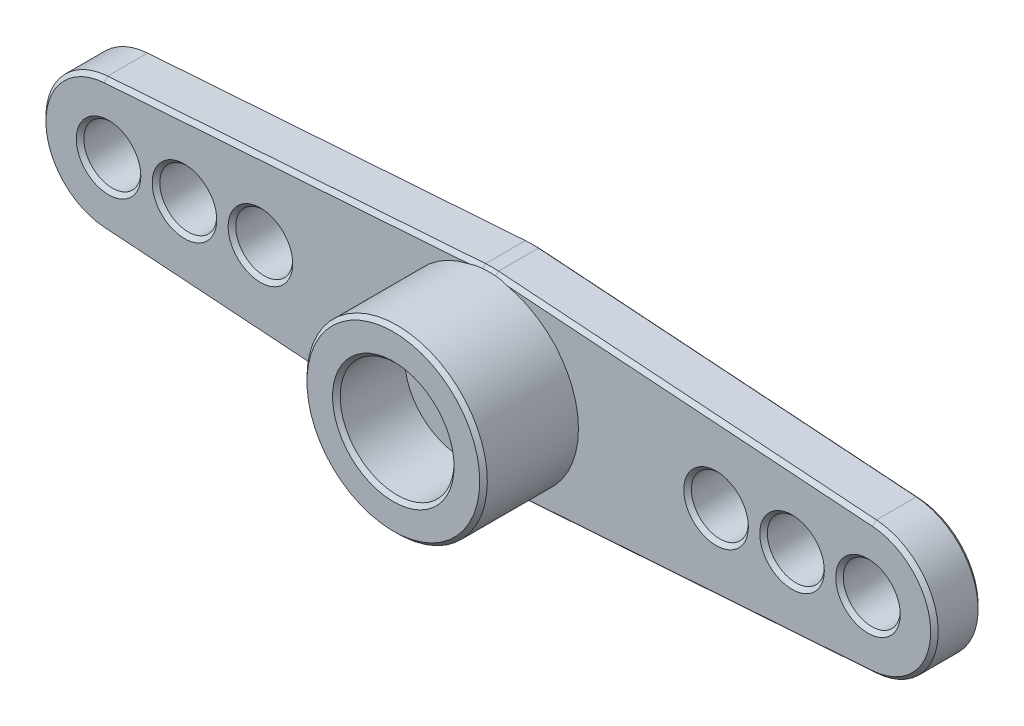
SolidWorks part; units mm, degrees
ref_plane "前视基准面" through (0, 0, 0) normal (0, 0, 1) x (1, 0, 0)
ref_plane "上视基准面" through (0, 0, 0) normal (0, 1, 0) x (1, 0, 0)
ref_plane "右视基准面" through (0, 0, 0) normal (1, 0, 0) x (0, 0, -1)
sketch "草图1" plane through (0, 0, 0) normal (0, 0, 1) x (1, 0, 0)
  line L0 (0.343, 4.888) -> (20.245, 3.4914)
  line L1 (0, 4.9) -> (0, -7.2758) construction
  line L2 (0, 0) -> (11.5337, 0) construction
  line L3 (0.343, -4.888) -> (20.245, -3.4914)
  line L4 (-0.343, -4.888) -> (-20.245, -3.4914)
  line L5 (-0.343, 4.888) -> (-20.245, 3.4914)
  arc A0 (-0.343, -4.888) -> (0.343, -4.888) centre (0, 0) ccw
  arc A1 (20.245, 3.4914) -> (20.245, -3.4914) centre (20, 0) cw
  arc A2 (-20.245, 3.4914) -> (-20.245, -3.4914) centre (-20, 0) ccw
  arc A3 (0.343, 4.888) -> (-0.343, 4.888) centre (0, 0) ccw
  circle A4 centre (-12, 0) radius 1.5
  circle A5 centre (-16, 0) radius 1.5
  circle A6 centre (-20, 0) radius 1.5
  circle A7 centre (20, 0) radius 1.5
  circle A8 centre (16, 0) radius 1.5
  circle A9 centre (12, 0) radius 1.5
  dimension "D1" = 9.8
  dimension "D2" = 47
  dimension "D3" = 3.5
  dimension "D4" = 12
  dimension "D5" = 4
  dimension "D6" = 8
  dimension "D7" = 3
  dimension "D8" = 3
  dimension "D9" = 3
  dimension "D10" = 2
extrude "凸台-拉伸1" add sketch "草图1" along normal blind 2.5 contours A4 | A8 | A7 | L5 A2 L4 A0 L3 A1 L0 A3 | A6 | A5 | A9 region at (-12, 0, 0) region at (20, 0, 0) region at (16, 0, 0)
sketch "草图2" plane through (0, 0, 2.5) normal (0, 0, 1) x (1, 0, 0)
  circle A0 centre (0, 0) radius 4.75
  dimension "D1" = 9.5
extrude "凸台-拉伸2" add sketch "草图2" along normal blind 5
sketch "草图3" plane through (0, 0, 7.5) normal (0, 0, 1) x (1, 0, 0)
  circle A0 centre (0, 0) radius 3
  dimension "D1" = 6
extrude "切除-拉伸1" cut sketch "草图3" against normal blind 3.6
sketch "草图4" plane through (0, 0, 0) normal (0, 0, -1) x (-1, 0, 0)
  circle A0 centre (0, 0) radius 3
  dimension "D1" = 6
extrude "切除-拉伸2" cut sketch "草图4" against normal blind 2.2
sketch "草图5" plane through (0, 0, 2.2) normal (0, 0, -1) x (-1, 0, 0)
  circle A0 centre (0, 0) radius 1.5
  dimension "D1" = 3
extrude "切除-拉伸3" cut sketch "草图5" against normal blind 3
chamfer "倒角1" distance 0.2 angle 45 33 edges at (4.75, 0, 7.5) (3, 0, 7.5) (-14.5, 0, 0) (-18.5, 0, 0) (-10.5, 0, 0) (-10.294, 4.1897, 0) (-23.5, 0, 0) (-10.294, -4.1897, 0) (0, -4.9, 0) (10.294, -4.1897, 0) (23.5, 0, 0) (10.294, 4.1897, 0) (0, 4.9, 0) (17.5, 0, 0) (21.5, 0, 0) (10.5, 0, 0) (-3, 0, 0) (1.5, 0, 3.9) (-1.5, 0, 2.2) (21.5, 0, 2.5) (17.5, 0, 2.5) (10.5, 0, 2.5) (-18.5, 0, 2.5) (-14.5, 0, 2.5) (-10.5, 0, 2.5) (10.294, -4.1897, 2.5) (23.5, 0, 2.5) (0, -4.9, 2.5) (10.294, 4.1897, 2.5) (-10.294, -4.1897, 2.5) (0, 4.9, 2.5) (-23.5, 0, 2.5) (-10.294, 4.1897, 2.5)
